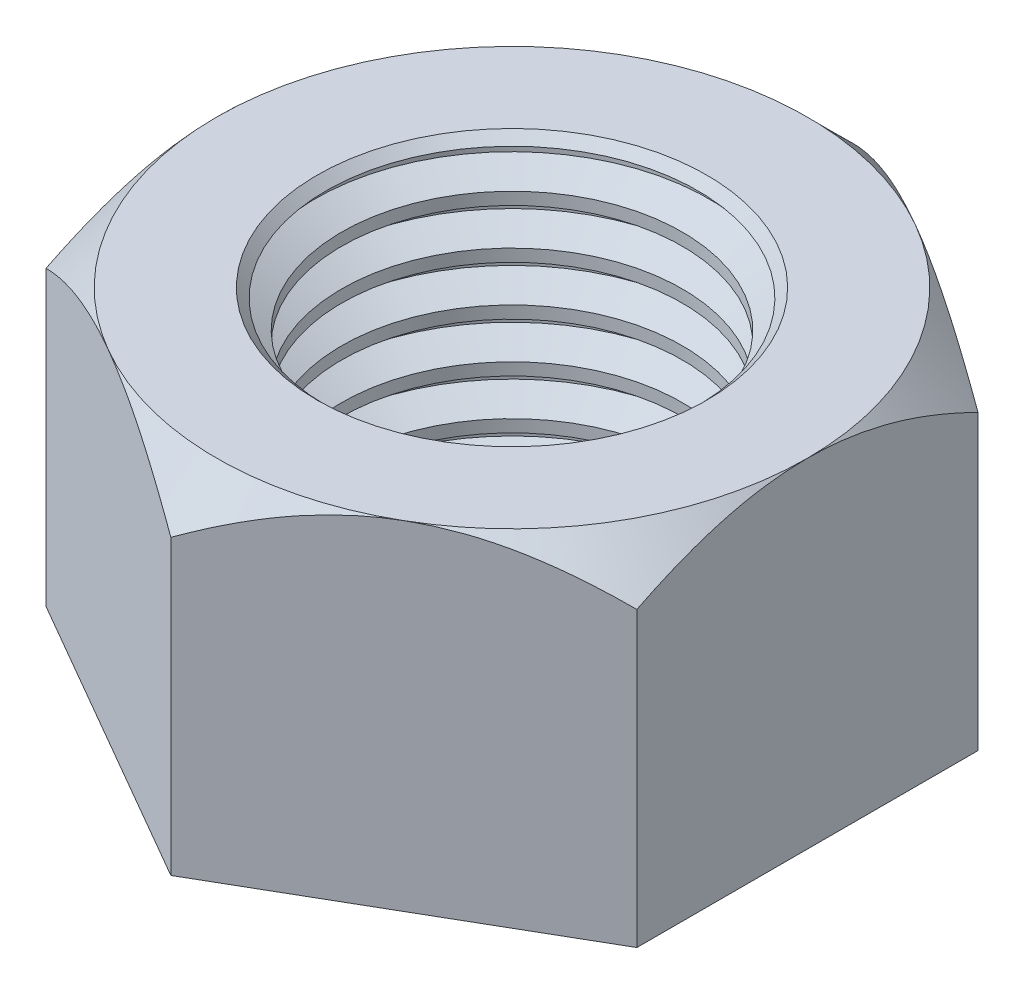
SolidWorks part; units mm, degrees
ref_plane "Front" through (0, 0, 0) normal (0, 0, 1) x (1, 0, 0)
ref_plane "Top" through (0, 0, 0) normal (0, 1, 0) x (1, 0, 0)
ref_plane "Right" through (0, 0, 0) normal (1, 0, 0) x (0, 0, -1)
sketch "Sketch1" plane through (0, 0, 0) normal (0, 1, 0) x (1, 0, 0)
  line L1 (0, 21.997) -> (-19.05, 10.9985)
  line L2 (-19.05, 10.9985) -> (-19.05, -10.9985)
  line L3 (-19.05, -10.9985) -> (0, -21.997)
  line L4 (0, -21.997) -> (19.05, -10.9985)
  line L5 (19.05, -10.9985) -> (19.05, 10.9985)
  line L6 (19.05, 10.9985) -> (0, 21.997)
  circle A0 centre (0, 0) radius 19.05 construction
  dimension "Hex Flats" = 38.1
extrude "Extrude1" add sketch "Sketch1" along normal blind 21.8281
sketch "Sketch3" plane through (0, 0, 0) normal (1, 0, 0) x (0, 0, -1)
  line L0 (19.05, 21.8281) -> (21.997, 18.8811)
  line L1 (10.9985, 21.8281) -> (21.997, 21.8281) construction
  line L2 (21.997, 21.8281) -> (21.997, 0) construction
  line L3 (21.997, 18.8811) -> (21.997, 21.8281)
  line L4 (21.997, 21.8281) -> (19.05, 21.8281)
  line L5 (0, 0.542) -> (0, -0.542) construction
  dimension "D1" = 45
  dimension "D2" = 38.1
revolve "Cut-Revolve2" cut sketch "Sketch3" angle 360 about L5
sketch "Sketch2" plane through (0, 0, 0) normal (0, 0, 1) x (1, 0, 0)
  line L0 (0, 1.6636) -> (0, -0.3796) construction
  line L1 (0, 21.8281) -> (10.9815, 21.8281)
  line L3 (0, 21.8281) -> (19.05, 21.8281) construction
  line L4 (0, 18.6531) -> (10.9815, 18.6531)
  line L5 (10.9815, 21.8281) -> (12.7, 20.8359)
  line L6 (12.7, 20.8359) -> (12.7, 20.4391)
  line L7 (12.7, 20.4391) -> (10.9815, 19.4469)
  line L9 (10.9815, 18.6531) -> (10.9815, 19.4469)
  line L10 (0, 18.6531) -> (0, 21.8281)
  line L11 (10.9815, 21.8281) -> (10.9815, 19.4469) construction
  line L12 (12.7, 20.6375) -> (10.9815, 20.6375) construction
  dimension "D1" = 60
  dimension "D2" = 0.7937
  dimension "D5" = 0.3969
  dimension "Pitch" = 3.175
  dimension "Major Dia." = 25.4
revolve "Cut-Revolve1" cut sketch "Sketch2" angle 360 about L0
pattern_linear "LPattern2" count 7 spacing 3.175 along (0, -1, 0) of "Cut-Revolve1"
chamfer "Chamfer1" distance 1.5875 angle 45 1 edges at (0, 21.8281, 10.9815) first distance on face at (0, 21.8281, 0)
equation "\"D5@Sketch2\"=\"Pitch@Sketch2\"/8"
equation "\"D2@Sketch2\"=\"Pitch@Sketch2\"/4"
equation "\"D3@LPattern2\"=\"Pitch@Sketch2\""
equation "\"D1@LPattern2\"=int(\"Height@Extrude1\"/\"Pitch@Sketch2\")+1"
equation "\"D2@Sketch3\"=\"Hex Flats@Sketch1\""
equation "\"D1@Chamfer1\"=\"Pitch@Sketch2\"/2"
